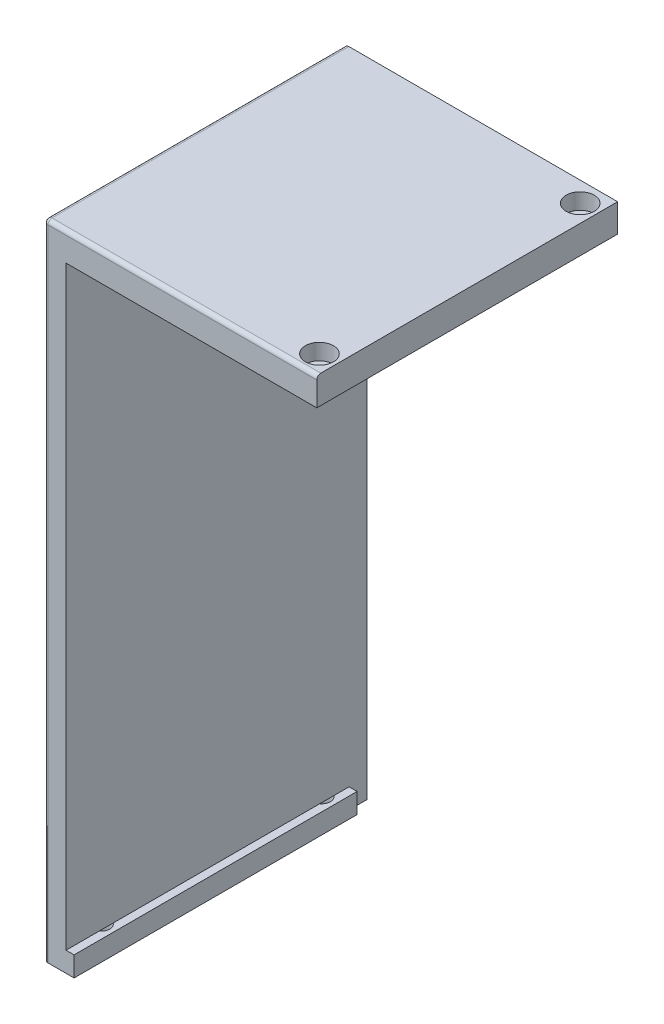
SolidWorks part; units mm, degrees
ref_plane "Front Plane" through (0, 0, 0) normal (0, 0, 1) x (1, 0, 0)
ref_plane "Top Plane" through (0, 0, 0) normal (0, 1, 0) x (1, 0, 0)
ref_plane "Right Plane" through (0, 0, 0) normal (1, 0, 0) x (0, 0, -1)
sketch "Sketch2" plane through (0, 0, 0) normal (0, 0, 1) x (1, 0, 0)
  line L0 (-88.5, -160.3461) -> (-88.5, -7)
  line L1 (-88.5, -7) -> (-26, -7)
  line L2 (-26, -7) -> (-26, 0)
  line L3 (-26, 0) -> (-93, 0)
  line L4 (-88.5, -160.3461) -> (-94, -160.3461)
  line L5 (-94, -160.3461) -> (-94, -1)
  arc A0 (-93, 0) -> (-94, -1) centre (-93, -1) ccw construction
  arc A1 (-93, 0) -> (-94, -1) centre (-93, -1) ccw
extrude "Boss-Extrude1" add sketch "Sketch2" along normal up to surface (75 mm away)
sketch "Sketch4" plane through (0, 0, 0) normal (0, 1, 0) x (1, 0, 0)
  circle A0 centre (-30.3417, -5) radius 2.05
  circle A1 centre (-30.3417, -70) radius 2.05
  circle A2 centre (-30.3417, -70) radius 2.15 construction
  circle A3 centre (-30.3417, -5) radius 2.15 construction
  circle A4 centre (-30.3417, -5) radius 3.5
  circle A5 centre (-30.3417, -70) radius 3.5
  dimension "D1" = 4.1
  dimension "D2" = 7
extrude "Cut-Extrude2" cut sketch "Sketch4" against normal up to next contours A0 | A1 region at (-30.3417, 0, 5) region at (-30.3417, 0, 70)
extrude "Cut-Extrude3" cut sketch "Sketch4<3>" against normal blind 4
sketch "Sketch4<3>" plane through (0, 0, 0) normal (0, 1, 0) x (1, 0, 0) same geometry as "Sketch4"
sketch "Sketch5" plane through (-88.5, 0, 0) normal (1, 0, 0) x (0, 0, -1)
  line L1 (-75, -160.3461) -> (-4.4481, -160.3461)
  line L2 (-75, -160.3461) -> (-75, -155.3461)
  line L3 (-75, -155.3461) -> (-4.4481, -155.3461)
  line L4 (-4.4481, -160.3461) -> (-4.4481, -155.3461)
  line L6 (0, -160.3461) -> (0, -7) construction
  dimension "D1" = 4.4481
  dimension "D2" = 5
extrude "Boss-Extrude2" add sketch "Sketch5" along normal blind 2
sketch "Sketch6" plane through (0, -160.3461, 0) normal (0, -1, 0) x (1, 0, 0)
  circle A0 centre (-89.75, 10) radius 2.15
  circle A1 centre (-89.75, 65) radius 2.15
  dimension "D1" = 4.3
extrude "Cut-Extrude4" cut sketch "Sketch6" against normal up to surface (5 mm away) up to face at (-87.5, -155.3461, 39.724)
fillet "Fillet1" radius 1 3 edges at (-59.5, 0, 75) (-93.7071, -0.2929, 75) (-94, -80.6731, 75)
